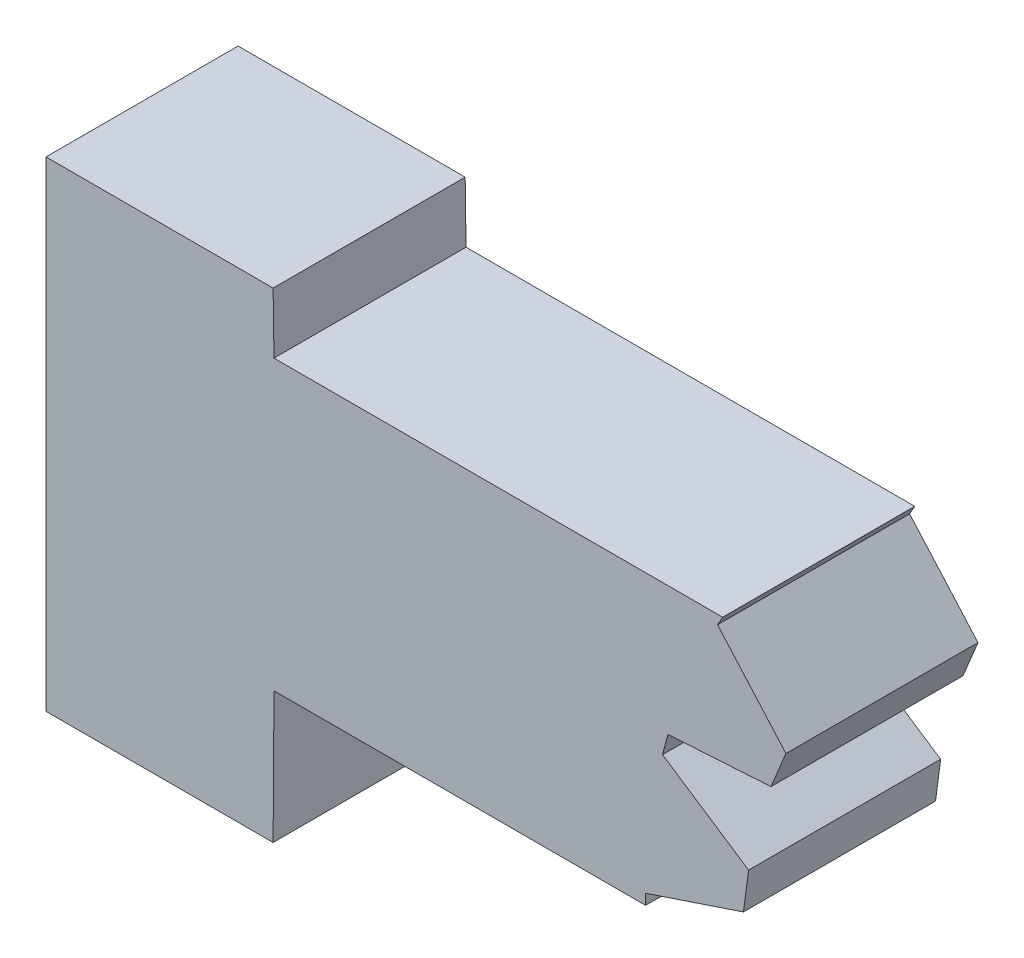
SolidWorks part; units mm, degrees
ref_plane "Front Plane" through (0, 0, 0) normal (0, 0, 1) x (1, 0, 0)
ref_plane "Top Plane" through (0, 0, 0) normal (0, 1, 0) x (1, 0, 0)
ref_plane "Right Plane" through (0, 0, 0) normal (1, 0, 0) x (0, 0, -1)
sketch "Sketch1" plane through (0, 0, 0) normal (0, 0, 1) x (1, 0, 0)
  line L0 (4.7478, 2.7448) -> (12.4871, 2.7448)
  line L1 (4.7478, 2.7448) -> (4.73, 0)
  line L2 (4.7478, 8.7448) -> (14.0928, 8.7448)
  line L3 (12.4871, 2.7448) -> (12.4871, 2.9629)
  line L4 (4.73, 0) -> (0, 0)
  line L5 (12.4871, 2.9629) -> (14.5257, 3.6448)
  line L6 (14.5257, 3.6448) -> (14.6321, 4.4531)
  line L7 (14.6321, 4.4531) -> (12.8395, 5.6394)
  line L8 (12.8395, 5.6394) -> (12.9523, 6.0607)
  line L9 (12.9523, 6.0607) -> (15.098, 6.1918)
  line L10 (15.098, 6.1918) -> (15.41, 6.9451)
  line L11 (15.41, 6.9451) -> (13.9855, 8.5549)
  line L12 (13.9855, 8.5549) -> (14.0928, 8.7448)
  line L13 (4.73, 10) -> (0, 10)
  line L14 (0, 0) -> (0, 10)
  line L15 (4.73, 10) -> (4.7478, 8.7448)
  dimension "D1" = 4.73
  dimension "D2" = 4.7478
  dimension "D23" = 10
  dimension "D13" = 2.7448
  dimension "D3" = 1.2552
  dimension "D4" = 9.345
  dimension "D5" = 0.4362
  dimension "D6" = 2.1496
  dimension "D7" = 0.8153
  dimension "D8" = 0.2181
  dimension "D9" = 8.5549
  dimension "D10" = 6.9451
  dimension "D11" = 6.1918
  dimension "D12" = 6.0607
  dimension "D14" = 5.6394
  dimension "D15" = 4.4531
  dimension "D16" = 3.6448
extrude "Boss-Extrude1" add sketch "Sketch1" along normal blind 4
equation "\"D4@Sketch1\" = \"ThumbLinkLengthMCP@Sketch1@thumbMovingBracketDown<1>.Part@thumbMovingMechanism<1>.Assembly@thumbMovingAssembly<1>.Assembly\" - 10.7'Toothed Mechanism"
